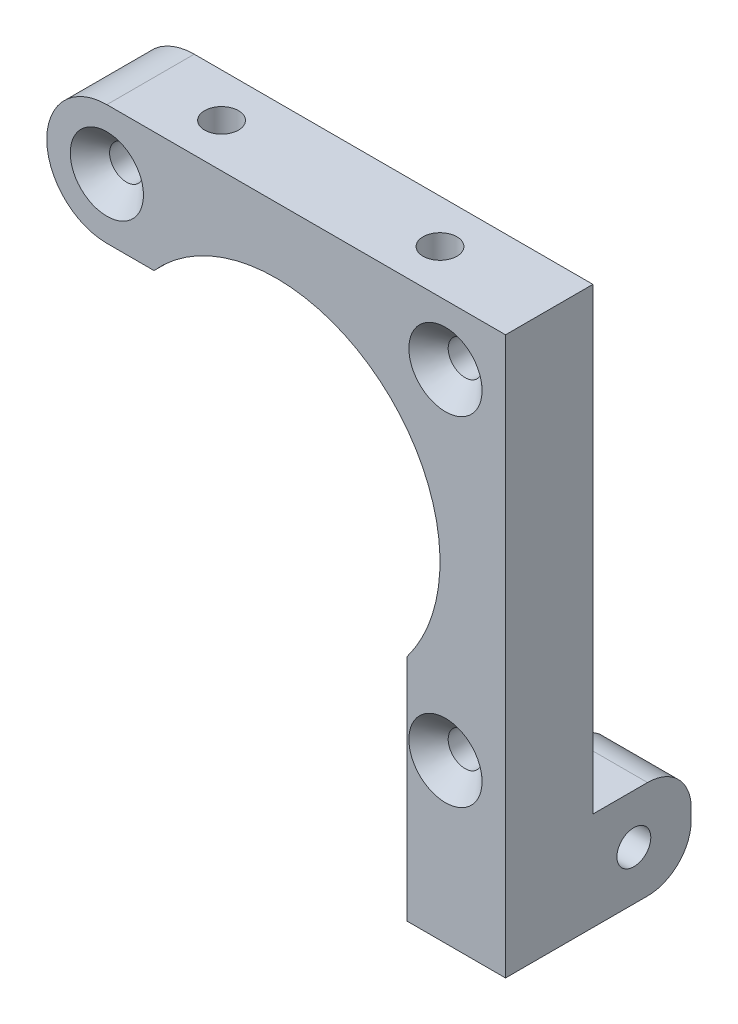
SolidWorks part; units mm, degrees
ref_plane "Front Plane" through (0, 0, 0) normal (0, 0, 1) x (1, 0, 0)
ref_plane "Top Plane" through (0, 0, 0) normal (0, 1, 0) x (1, 0, 0)
ref_plane "Right Plane" through (0, 0, 0) normal (1, 0, 0) x (0, 0, -1)
sketch "Sketch1" plane through (0, 0, 0) normal (0, 0, 1) x (1, 0, 0)
  line L0 (-21, 21) -> (21, 21) construction
  line L1 (-21, 21) -> (-21, -21) construction
  line L2 (21, 21) -> (21, -21) construction
  line L3 (-21, -21) -> (21, -21) construction
  line L4 (-21, 21) -> (21, -21) construction
  line L5 (21, 21) -> (-21, -21) construction
  line L7 (-15.5, 10) -> (-11.1803, 10)
  line L8 (-15.5, 21) -> (21, 21)
  line L9 (21, 21) -> (21, -30)
  line L10 (21, -30) -> (12, -30)
  line L11 (12, -30) -> (12, -9)
  line L12 (15.5, 15.5) -> (15.5, -15.5) construction
  line L13 (15.5, 15.5) -> (-22.9774, 15.5) construction
  circle A0 centre (0, 0) radius 11 construction
  arc A1 (12, -9) -> (-11.1803, 10) centre (0, 0) ccw
  circle A2 centre (15.5, 15.5) radius 1.55
  circle A3 centre (15.5, -15.5) radius 1.55
  circle A4 centre (-15.5, 15.5) radius 1.55
  arc A6 (-15.5, 21) -> (-15.5, 10) centre (-15.5, 15.5) ccw
  point P1 (0, 0)
  dimension "D2" = 22
  dimension "D3" = 3.1
  dimension "D5" = 9
  dimension "D7" = 15
  dimension "D1" = 42
  dimension "D4" = 31
  dimension "D6" = 9
extrude "Boss-Extrude1" add sketch "Sketch1" along normal blind 8
sketch "Sketch2" plane through (0, 21, 0) normal (0, 1, 0) x (1, 0, 0)
  line L0 (21, -4) -> (-9, -4) construction
  line L1 (21, -8) -> (21, 0) construction
  circle A0 centre (-9, -4) radius 1.55
  circle A1 centre (11, -4) radius 1.55
  dimension "D1" = 3.1
  dimension "D3" = 10
  dimension "D2" = 20
extrude "Cut-Extrude1" cut sketch "Sketch2" against normal through all
sketch "Sketch3" plane through (0, 0, 0) normal (0, 0, -1) x (-1, 0, 0)
  line L0 (-12, -9) -> (-12, -30) construction
  line L1 (-21, -30) -> (-12, -30)
  line L2 (-21, -30) -> (-21, -21)
  line L3 (-21, -21) -> (-12, -21)
  line L4 (-12, -30) -> (-12, -21)
  line L5 (-21, 21) -> (15.5, 21) construction
  dimension "D1" = 42
extrude "Boss-Extrude2" add sketch "Sketch3" along normal blind 9
sketch "Sketch4" plane through (21, 0, 0) normal (1, 0, 0) x (0, 0, -1)
  line L0 (9, -25.5) -> (3.75, -25.5) construction
  line L1 (9, -21) -> (9, -30) construction
  circle A0 centre (3.75, -25.5) radius 1.55
  dimension "D1" = 3.1
  dimension "D2" = 3.75
extrude "Cut-Extrude2" cut sketch "Sketch4" against normal through all
fillet "Fillet1" radius 4 2 edges at (16.5, -21, -9) (16.5, -30, -9)
sketch "Sketch5" plane through (0, 21, 0) normal (0, 1, 0) x (1, 0, 0)
  line L0 (-12, -4) -> (-12, 2.1732)
  line L1 (-12, 2.1732) -> (-6, 2.1732)
  line L2 (-6, 2.1732) -> (-6, -4)
  line L3 (8, -4) -> (8, 2.1892)
  line L4 (8, 2.1892) -> (14, 2.1892)
  line L5 (14, 2.1892) -> (14, -4)
  arc A0 (8, -4) -> (14, -4) centre (11, -4) ccw
  arc A1 (-12, -4) -> (-6, -4) centre (-9, -4) ccw
  circle A2 centre (-9, -4) radius 1.55 construction
  circle A3 centre (11, -4) radius 1.55 construction
  arc A4 (-6, -4) -> (-12, -4) centre (-9, -4) ccw construction
  arc A5 (14, -4) -> (8, -4) centre (11, -4) ccw construction
  dimension "D1" = 6
extrude "Cut-Extrude3" cut sketch "Sketch5" against normal up to next from offset 7 offset against normal yes
chamfer "Chamfer1" distance 1.8 angle 45 3 edges at (17.05, -15.5, 8) (-13.95, 15.5, 8) (17.05, 15.5, 8)
chamfer "Chamfer2" distance 1.8 angle 45 2 edges at (9.45, 14, 4) (-10.55, 14, 4)
sketch "Sketch6" plane through (12, 0, 0) normal (-1, 0, 0) x (0, 0, 1)
  line L0 (-3.75, -22.15) -> (-3.75, -21)
  line L1 (-5, -21) -> (0, -21) construction
  line L2 (-3.75, -28.85) -> (-3.75, -30)
  line L3 (2.8157, -30) -> (-5, -30) construction
  line L4 (-3.75, -21) -> (-10.3659, -21)
  line L5 (-10.3659, -21) -> (-10.3659, -30)
  line L6 (-10.3659, -30) -> (-3.75, -30)
  arc A0 (-3.75, -28.85) -> (-3.75, -22.15) centre (-3.75, -25.5) ccw
  circle A1 centre (-3.75, -25.5) radius 1.55 construction
  dimension "D1" = 6.7
extrude "Cut-Extrude4" cut sketch "Sketch6" against normal offset from surface (2 mm away) 7 up to face at (21, -23.95, -3.75)
chamfer "Chamfer3" distance 1.8 angle 45 1 edges at (14, -27.05, -3.75)
chamfer "Chamfer4" distance 3.5 distance2 2 1 edges at (12, -29.425, -3.75) first distance on face at (12, -20.625, -0.9867)
